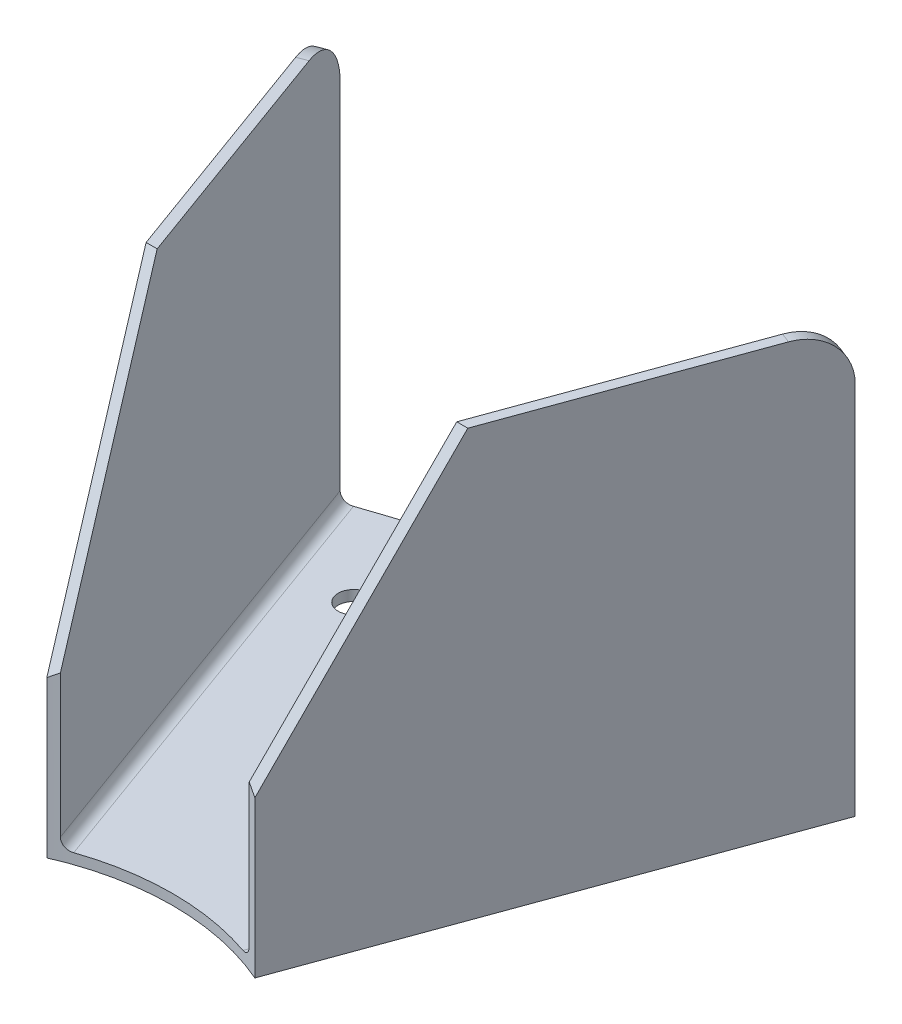
SolidWorks part; units mm, degrees
ref_plane "Front Plane" through (0, 0, 0) normal (0, 0, 1) x (1, 0, 0)
ref_plane "Top Plane" through (0, 0, 0) normal (0, 1, 0) x (1, 0, 0)
ref_plane "Right Plane" through (0, 0, 0) normal (1, 0, 0) x (0, 0, -1)
sketch "Sketch1" plane through (0, 0, 0) normal (0, 1, 0) x (1, 0, 0)
  line L4 (-10, 22.9129) -> (-25.4016, 65.2285)
  line L5 (10, 22.9129) -> (25.4016, 65.2285)
  line L6 (0, 0) -> (0, 40.3478) construction
  line L7 (-24.4671, 65.5848) -> (-9.0748, 23.2948)
  line L8 (9.0748, 23.2948) -> (24.4671, 65.5848)
  arc A0 (10, 22.9129) -> (-10, 22.9129) centre (0, 0) ccw
  arc A1 (25.4016, 65.2285) -> (-25.4016, 65.2285) centre (0, 0) ccw
  point P1 (0, 25)
  point P10 (-9.0603, 23.2549)
  point P12 (-24.4619, 65.5705)
  point P13 (9.0603, 23.2549)
  point P14 (24.4619, 65.5705)
  dimension "D1" = 50
  dimension "D2" = 140
  dimension "D3" = 20
  dimension "D4" = 20
  dimension "D5" = 20
  dimension "D6" = 1
  dimension "D7" = 1
extrude "Boss-Extrude2" add sketch "Sketch1" along normal blind 40 contours L7 A1 L4 A0 | L5 A1 L8 A0 region at (-17.2367, 0, -44.2573) region at (17.2367, 0, -44.2573)
extrude "Boss-Extrude3" add sketch "Sketch1<5>" against normal blind 1 contours L8 A1 L7 A0 | L5 A1 L8 A0 | L7 A1 L4 A0 region at (-17.2367, 0, -44.2573) region at (0, 0, -49.8429) region at (17.2367, 0, -44.2573)
sketch "Sketch1<5>" plane through (0, 0, 0) normal (0, 1, 0) x (1, 0, 0) same geometry as "Sketch1"
fillet "Fillet1" radius 1 2 edges at (16.771, 0, -44.4398) (-16.771, 0, -44.4398)
fillet "Fillet2" radius 5 2 edges at (-24.935, 40, -65.4083) (24.935, 40, -65.4083)
sketch "Sketch3" plane through (0, 0, 0) normal (1, 0, 0) x (0, 0, -1)
  line L0 (22.9129, 14) -> (37.924, 40)
  line L1 (37.924, 40) -> (22.9129, 40)
  line L4 (22.9129, 14) -> (17.7234, 14)
  line L5 (17.7234, 14) -> (17.7234, 40)
  line L6 (17.7234, 40) -> (22.9129, 40)
  dimension "D2" = 15
extrude "Cut-Extrude1" cut sketch "Sketch3" against normal through all both and the other way through all
sketch "Sketch4" plane through (0, 0, 0) normal (0, 1, 0) x (1, 0, 0)
  line L0 (-15.5291, 57.9555) -> (0, 0) construction
  line L1 (15.5291, 57.9555) -> (0, 0) construction
  line L2 (0, 40) -> (0, 0) construction
  circle A0 centre (0, 40) radius 1.5
  circle A1 centre (-15.5291, 57.9555) radius 1.5
  circle A2 centre (15.5291, 57.9555) radius 1.5
  point P6 (0, 0)
  dimension "D6" = 3
  dimension "D1" = 15
  dimension "D2" = 15
  dimension "D3" = 40
  dimension "D4" = 60
  dimension "D5" = 60
extrude "Cut-Extrude2" cut sketch "Sketch4" against normal up to surface (1 mm away) up to face at (0, -1, -45.7853)
